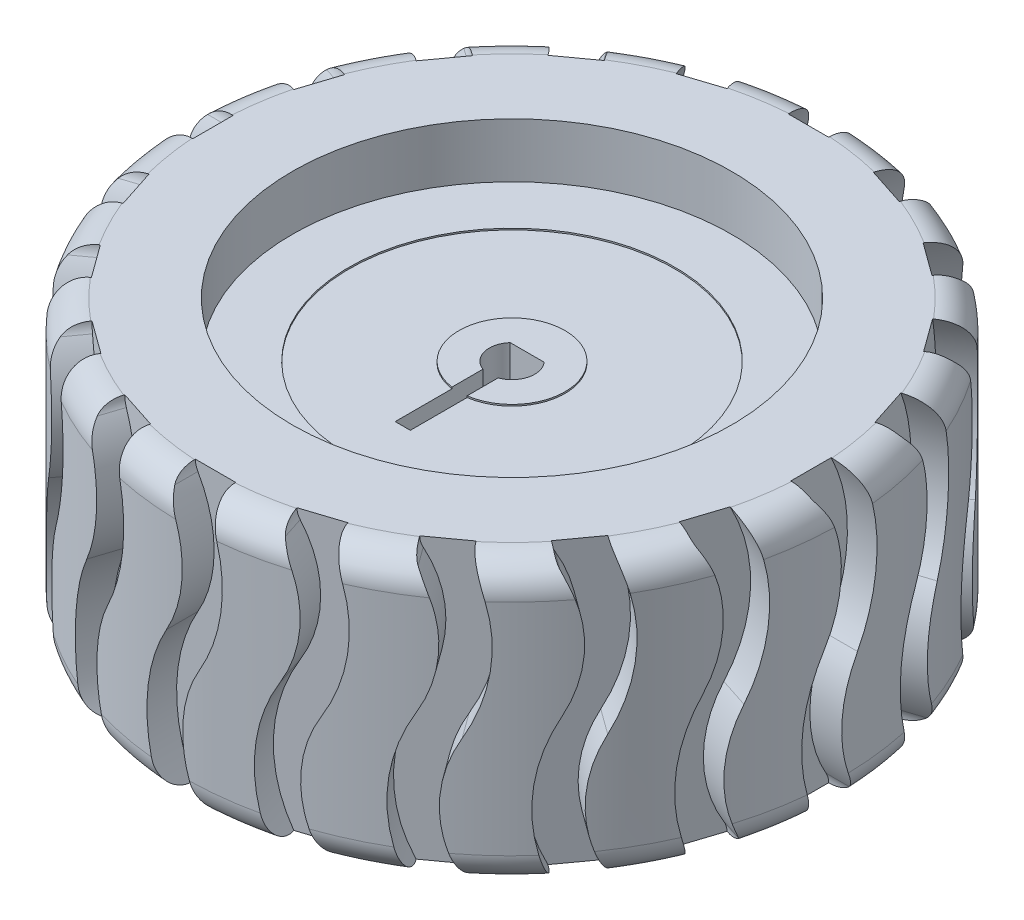
SolidWorks part; units mm, degrees
ref_plane "Front Plane" through (0, 0, 0) normal (0, 0, 1) x (1, 0, 0)
ref_plane "Top Plane" through (0, 0, 0) normal (0, 1, 0) x (1, 0, 0)
ref_plane "Right Plane" through (0, 0, 0) normal (1, 0, 0) x (0, 0, -1)
sketch "Sketch1" plane through (0, 0, 0) normal (0, 1, 0) x (1, 0, 0)
  circle A0 centre (0, 0) radius 21.75
  dimension "D1" = 43.5
extrude "Boss-Extrude1" add sketch "Sketch1" along normal blind 18.5
fillet "Fillet1" radius 2 2 edges at (0, 0, 21.75) (0, 18.5, 21.75)
sketch "Sketch2" plane through (0, 18.5, 0) normal (0, 1, 0) x (1, 0, 0)
  circle A0 centre (0, 0) radius 14.5
  dimension "D1" = 29
extrude "Cut-Extrude1" cut sketch "Sketch2" against normal blind 3.6
sketch "Sketch3" plane through (0, 0, 0) normal (0, -1, 0) x (1, 0, 0)
  circle A0 centre (0, 0) radius 14.5
  dimension "D1" = 29
extrude "Cut-Extrude2" cut sketch "Sketch3" against normal blind 7.1 contours A0
sketch "Sketch4" plane through (0, 7.1, 0) normal (0, -1, 0) x (1, 0, 0)
  line L0 (-1.3034, 11.929) -> (-1.575, 14.4142)
  line L1 (1.3034, 11.929) -> (1.575, 14.4142)
  line L2 (0, -1000) -> (0, 0) construction
  line L3 (0, 12) -> (0, 1018.2764) construction
  arc A0 (1.575, 14.4142) -> (-1.575, 14.4142) centre (0, 0) ccw
  circle A1 centre (0, 0) radius 14.5 construction
  arc A2 (1.3034, 11.929) -> (-1.3034, 11.929) centre (0, 0) ccw
  point P8 (0, 0)
  dimension "D1" = 2.5
  dimension "D2" = 3.15
  dimension "D3" = 2.5
extrude "Boss-Extrude2" add sketch "Sketch4" along normal blind 6.5
pattern_circular "CirPattern1" count 12 over 360 about axis through (0, 0, 0) along (0, -1, 0) of "Boss-Extrude2"
sketch "Sketch5" plane through (0, 7.1, 0) normal (0, -1, 0) x (1, 0, 0)
  circle A0 centre (0, 0) radius 12
  arc A1 (7.0933, 9.6791) -> (4.8357, 10.9825) centre (0, 0) ccw construction
extrude "Cut-Extrude3" cut sketch "Sketch5" against normal blind 6
sketch "Sketch6" plane through (0, 13.1, 0) normal (0, -1, 0) x (1, 0, 0)
  circle A0 centre (0, 0) radius 4
  dimension "D1" = 8
extrude "Boss-Extrude3" add sketch "Sketch6" along normal blind 6
sketch "Sketch8" plane through (0, 0, 0) normal (0, 0, 1) x (1, 0, 0)
  line L0 (3.5, 9.1) -> (3.5, 13.1)
  line L1 (3.5, 13.1) -> (12.5, 13.1)
  line L2 (12.5, 13.1) -> (12.5, 11.1)
  line L3 (12.5, 11.1) -> (3.5, 9.1)
  line L5 (-4, 13.1) -> (4, 13.1) construction
  point P8 (0, 0)
  dimension "D1" = 2
  dimension "D2" = 4
  dimension "D3" = 3.5
  dimension "D4" = 12.5
extrude "Boss-Extrude5" add sketch "Sketch8" along normal blind 0.75 and the other way blind 0.75
pattern_circular "CirPattern2" count 6 over 360 about axis through (0, 0, 0) along (0, -1, 0) of "Boss-Extrude5"
sketch "Sketch9" plane through (0, 7.1, 0) normal (0, -1, 0) x (1, 0, 0)
  line L0 (-1.118, -1) -> (1.118, -1)
  arc A0 (1.118, -1) -> (-1.118, -1) centre (0, 0) ccw
  dimension "D1" = 3
  dimension "D2" = 1
extrude "Cut-Extrude4" cut sketch "Sketch9" against normal through all
sketch "Sketch10" plane through (0, 14.9, 0) normal (0, 1, 0) x (1, 0, 0)
  line L0 (0, 0) -> (0, -5.0525) construction
  line L1 (-0.5, 1) -> (0.5, 1)
  line L2 (-0.5, 1) -> (-0.5, -7.21)
  line L3 (-0.5, -7.21) -> (0.5, -7.21)
  line L4 (0.5, 1) -> (0.5, -7.21)
  line L5 (1.118, 1) -> (-1.118, 1) construction
  point P5 (0, 0)
  dimension "D1" = 1
  dimension "D2" = 8.21
extrude "Cut-Extrude5" cut sketch "Sketch10" against normal through all
sketch "Sketch11" plane through (0, 14.9, 0) normal (0, 1, 0) x (1, 0, 0)
  circle A0 centre (0, 0) radius 10.75
  circle A1 centre (0, 0) radius 3.5
  dimension "D1" = 7
  dimension "D2" = 21.5
extrude "Cut-Extrude6" cut sketch "Sketch11" against normal blind 0.1
ref_plane "Plane1" through (21.75, 0, 0) normal (1, 0, 0) x (0, 0, -1)
sketch "Sketch12" plane through (21.75, 0, 0) normal (1, 0, 0) x (0, 0, -1)
  line L0 (0, 18.6886) -> (0, 0) construction
  line L1 (14.5, 18.5) -> (-14.5, 18.5) construction
  line L7 (-8.0107, 13.875) -> (0, 18.5) construction
  arc A0 (0, 9.25) -> (0, 18.5) centre (-8.0107, 13.875) ccw construction
  arc A1 (0, 9.25) -> (0, 0) centre (8.0107, 4.625) ccw construction
  arc A2 (1.0825, 8.625) -> (1.0825, 0.625) centre (8.0107, 4.625) ccw
  arc A3 (1.0825, 8.625) -> (1.0825, 19.125) centre (-8.0107, 13.875) ccw
  arc A4 (-1.0825, 9.875) -> (-1.0825, -0.625) centre (8.0107, 4.625) ccw
  arc A5 (-1.0825, 9.875) -> (-1.0825, 17.875) centre (-8.0107, 13.875) ccw
  arc A6 (1.0825, 0.625) -> (-1.0825, -0.625) centre (0, 0) cw
  arc A7 (1.0825, 19.125) -> (-1.0825, 17.875) centre (0, 18.5) ccw
  point P5 (-0.3928, 14.7932)
  point P6 (0, 0)
  point P10 (0, 0)
  point P11 (0, 0)
  point P12 (0, 14)
  point P13 (0, 18.5)
  dimension "D1" = 1.25
  dimension "D2" = 1.25
extrude "Cut-Extrude8" cut sketch "Sketch12" against normal blind 2.1
pattern_circular "CirPattern3" count 20 over 360 about axis through (0, 7.1, 0) along (0, -1, 0) of "Cut-Extrude8"
